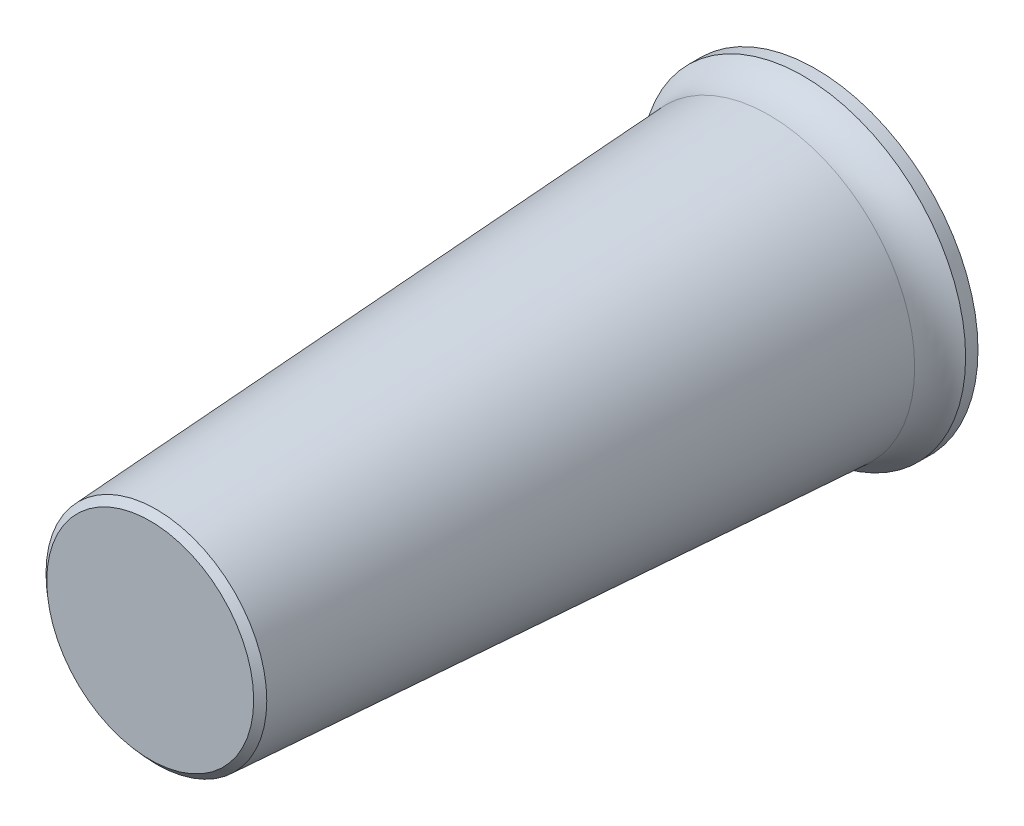
SolidWorks part; units mm, degrees
material "Polytetrafluorethylene"
ref_plane "Front Plane" through (0, 0, 0) normal (0, 0, 1) x (1, 0, 0)
ref_plane "Top Plane" through (0, 0, 0) normal (0, 1, 0) x (1, 0, 0)
ref_plane "Right Plane" through (0, 0, 0) normal (1, 0, 0) x (0, 0, -1)
ref_axis "CL" through (0, 0, 55) along (0, 0, -1)
sketch "Sketch1" plane through (0, 0, 0) normal (1, 0, 0) x (0, 0, -1)
  line L0 (-10.754, 0) -> (-0.754, 0)
  line L1 (-10.754, 0) -> (-10.7539, 1.7784)
  line L2 (-10.7539, 1.7784) -> (-0.7539, 2.355)
  line L3 (-0.7539, 2.355) -> (-0.754, 0) construction
  line L4 (-14.0337, 0) -> (7.5278, 0) construction
  line L5 (0, 0) -> (0, 2.6245)
  line L6 (-0.2, 2.6245) -> (0, 2.6245)
  line L7 (0, 0) -> (-0.754, 0)
  arc A0 (-0.7539, 2.355) -> (-0.2, 2.6245) centre (-0.8, 3.1537) ccw
  point P4 (-5.754, 0)
  point P7 (0, 0)
  point P10 (0, 0)
  point P12 (7.5278, 0)
  dimension "D4" = 0.8
  dimension "D1" = 10
  dimension "D2" = 3.3
  dimension "D3" = 4.71
  dimension "D5" = 0.754
  dimension "D6" = 0.2
revolve "Revolve1" add sketch "Sketch1" angle 360 about L4
chamfer "Chamfer1" distance 0.1 angle 45 1 edges at (1.7784, 0, 10.7539) first distance on face at (1.7784, 0, 10.7539)
